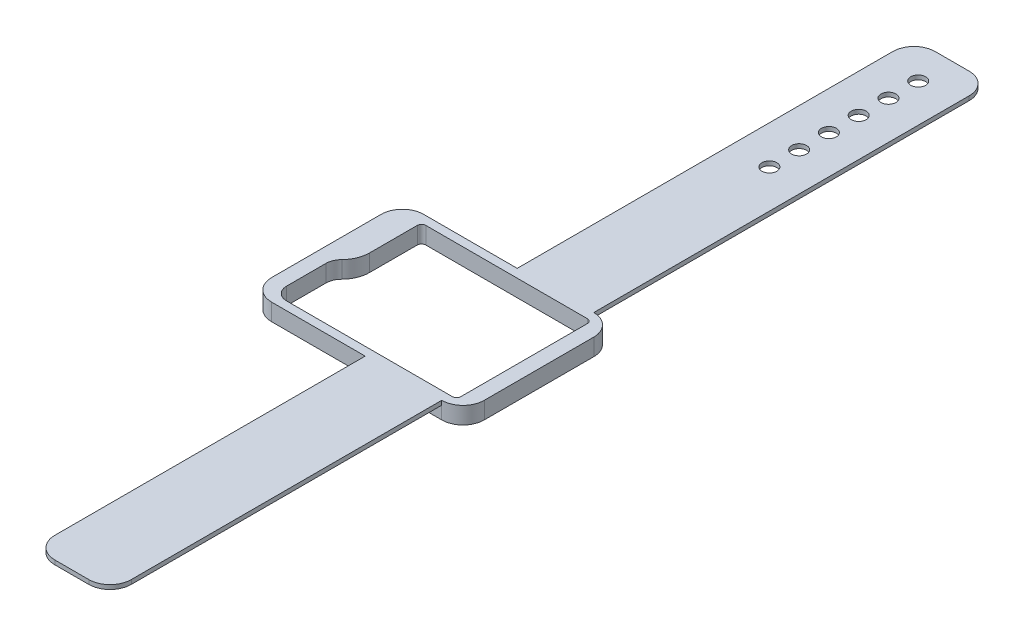
SolidWorks part; units mm, degrees
ref_plane "Front Plane" through (0, 0, 0) normal (0, 0, 1) x (1, 0, 0)
ref_plane "Top Plane" through (0, 0, 0) normal (0, 1, 0) x (1, 0, 0)
ref_plane "Right Plane" through (0, 0, 0) normal (1, 0, 0) x (0, 0, -1)
sketch "Sketch1" plane through (0, 0, 0) normal (0, 1, 0) x (1, 0, 0)
  line L0 (-27, 2) -> (0, 2)
  line L1 (0, 0) -> (18, 0) construction
  line L2 (0, 0) -> (0, 95.3) construction
  line L3 (0, 95.3) -> (18, 95.3)
  line L4 (18, 0) -> (18, 95.3) construction
  line L5 (-27, 0) -> (23, 0) construction
  line L6 (-27, 0) -> (-27, -31.75) construction
  line L7 (-27, -31.75) -> (23, -31.75) construction
  line L8 (23, 0) -> (23, -31.75) construction
  line L9 (0, -31.75) -> (18, -31.75) construction
  line L10 (0, -31.75) -> (0, -111.75) construction
  line L11 (0, -111.75) -> (18, -111.75)
  line L12 (18, -31.75) -> (18, -111.75) construction
  line L13 (-27, 2) -> (-27, -33.75)
  line L14 (-27, -33.75) -> (0, -33.75)
  line L15 (23, 2) -> (23, -33.75)
  line L16 (0, 95.3) -> (0, 2)
  line L17 (18, 95.3) -> (18, 2)
  line L18 (0, -33.75) -> (0, -111.75)
  line L19 (18, -33.75) -> (18, -111.75)
  line L20 (-23.5, -28.75) -> (-23.5, -19.4927)
  line L21 (-20.5, 0) -> (19.5, 0)
  line L22 (-20.5, 0) -> (-20.5, -31.75) construction
  line L23 (-20.5, -31.75) -> (19.5, -31.75)
  line L24 (19.5, 0) -> (19.5, -31.75)
  line L25 (-20.5, -12.2187) -> (-20.5, 0)
  line L26 (9, -111.75) -> (9, 95.3) construction
  line L27 (0, 42) -> (18, 42) construction
  line L28 (23, -33.75) -> (18, -33.75)
  line L29 (23, 2) -> (18, 2)
  arc A8 (-20.5, -31.75) -> (-23.5, -28.75) centre (-20.5, -28.75) cw
  arc A9 (-23.5, -19.4927) -> (-22.4064, -16.8412) centre (-19.7387, -19.4927) cw
  arc A10 (-22.4064, -16.8412) -> (-20.5, -12.2187) centre (-27.0572, -12.2187) ccw
  circle A11 centre (9, -103.75) radius 1.75
  circle A12 centre (9, 87.3) radius 1.75
  circle A13 centre (9, 80.3) radius 1.75
  circle A14 centre (9, 73.3) radius 1.75
  circle A15 centre (9, 66.3) radius 1.75
  circle A16 centre (9, 59.3) radius 1.75
  circle A17 centre (9, 52.3) radius 1.75
  point P14 (18, -35.2863)
  point P15 (-0.5469, -37.3039)
  point P16 (-27, -34.7533)
  point P17 (-27, -33.75)
  point P18 (-27.7975, 2)
  point P21 (-27, -33.5607)
  point P22 (0, 0)
  point P23 (23, -34.8211)
  point P27 (22.8204, -34.8211)
  point P28 (18.2305, 4.9836)
  point P29 (23, 0.6478)
  point P30 (23, 1.193)
  point P31 (0, 3.2909)
  point P33 (-0.5638, 3.2909)
  point P64 (-27, 2)
  point P65 (-26.8351, 2)
  point P66 (22.053, 3.3612)
  point P67 (0, 0)
  point P68 (0, 0)
  point P69 (20.4904, -34.7842)
  point P70 (0, 0)
  point P71 (19.5, -34.8761)
  point P72 (22.053, -31.3258)
  point P73 (18, -36.3048)
  point P74 (23, -30.7168)
  point P75 (22.0586, 2.7977)
  point P76 (0, 0)
  point P77 (18.1363, 16.3615)
  point P78 (22.4142, 5.5041)
  point P79 (18.2396, 14.594)
  point P80 (0, 0)
  point P81 (23, -0.738)
  point P82 (0, 0)
  point P83 (21.5792, -32.9319)
  point P84 (23, 0.9836)
  point P85 (0, 0)
  dimension "D10" = 3.5
  dimension "D12" = 7
  dimension "D18" = 2
  dimension "D19" = 2
  dimension "D1" = 95.3
  dimension "D2" = 31.75
  dimension "D3" = 80
  dimension "D4" = 5
  dimension "D5" = 18
  dimension "D6" = 50
  dimension "D7" = 3
  dimension "D8" = 40
  dimension "D9" = 8
  dimension "D11" = 8
  dimension "D13" = 7
  dimension "D14" = 7
  dimension "D15" = 42
  dimension "D16" = 7
  dimension "D17" = 7
  dimension "D20" = 3
extrude "Boss-Extrude1" add sketch "Sketch1" along normal blind 1
fillet "Fillet1" radius 5 4 edges at (0, 0.5, -95.3) (18, 0.5, -95.3) (0, 0.5, 111.75) (18, 0.5, 111.75)
sketch "Sketch2" plane through (0, 0, 0) normal (0, -1, 0) x (1, 0, 0)
  line L0 (-27, -2) -> (-27, 33.75) construction
  line L1 (23, 33.75) -> (23, -2) construction
  line L4 (19.5, 31.75) -> (19.5, 0) construction
  line L5 (19.5, 0) -> (-20.5, 0) construction
  line L6 (-20.5, 0) -> (-20.5, 12.2187) construction
  line L7 (-20.5, 31.75) -> (19.5, 31.75) construction
  line L8 (-23.5, 19.4927) -> (-23.5, 28.75) construction
  line L9 (-23.5, 19.4927) -> (-23.5, 28.75)
  line L10 (-20.5, 31.75) -> (19.5, 31.75)
  line L11 (-20.5, 0) -> (-20.5, 12.2187)
  line L12 (19.5, 0) -> (-20.5, 0)
  line L13 (19.5, 31.75) -> (19.5, 0)
  line L17 (-27, -2) -> (-27, 33.75)
  line L19 (23, 33.75) -> (23, -2)
  line L22 (23, 33.75) -> (-27, 33.75)
  line L23 (23, -2) -> (-27, -2)
  arc A0 (-23.5, 19.4927) -> (-22.4064, 16.8412) centre (-19.7387, 19.4927) ccw construction
  arc A8 (-20.5, 12.2187) -> (-22.4064, 16.8412) centre (-27.0572, 12.2187) ccw construction
  arc A9 (-20.5, 31.75) -> (-23.5, 28.75) centre (-20.5, 28.75) ccw construction
  arc A10 (-23.5, 19.4927) -> (-22.4064, 16.8412) centre (-19.7387, 19.4927) ccw
  arc A11 (-20.5, 31.75) -> (-23.5, 28.75) centre (-20.5, 28.75) ccw
  arc A12 (-20.5, 12.2187) -> (-22.4064, 16.8412) centre (-27.0572, 12.2187) ccw
  line M18 (23, -2) -> (23, 33.75)
  line M29 (-27, 33.75) -> (-27, -2)
  line M33 (-20.5, 0) -> (-20.5, 12.2187)
  arc M34 (-20.5, 12.2187) -> (-22.4064, 16.8412) centre (-27.0572, 12.2187) ccw
  arc M35 (-22.4064, 16.8412) -> (-23.5, 19.4927) centre (-19.7387, 19.4927) cw
  line M36 (-23.5, 19.4927) -> (-23.5, 28.75)
  arc M37 (-23.5, 28.75) -> (-20.5, 31.75) centre (-20.5, 28.75) cw
  line M38 (-20.5, 31.75) -> (19.5, 31.75)
  line M39 (19.5, 31.75) -> (19.5, 0)
  line M40 (19.5, 0) -> (-20.5, 0)
extrude "Boss-Extrude2" add sketch "Sketch2" along normal blind 3 contours M29 M18 M40 M33 M34 M35 M36 M37 M38 M39 region at (-26.3853, 0, 15.875)
fillet "Fillet3" radius 1 3 edges at (19.5, -1, 31.75) (-20.5, -1, 0) (19.5, -1, 0)
sketch "Sketch4" plane through (0, 1, 0) normal (0, 1, 0) x (1, 0, 0)
  circle A0 centre (9, -103.75) radius 1.5
  dimension "D1" = 3
extrude "Boss-Extrude3" add sketch "Sketch4" against normal blind 2.5 separate body
sketch "Sketch5" plane through (0, 1, 0) normal (0, 1, 0) x (1, 0, 0)
  circle A0 centre (9, -103.75) radius 1.75 construction
  circle A1 centre (9, -103.75) radius 1.75
extrude "Boss-Extrude4" add sketch "Sketch5" against normal up to surface (1 mm away) up to face at (9, 0, 105.5)
fillet "Fillet8" radius 5 4 edges at (-27, -1, -2) (-27, -1, 33.75) (23, -1, -2) (23, -1, 33.75)
